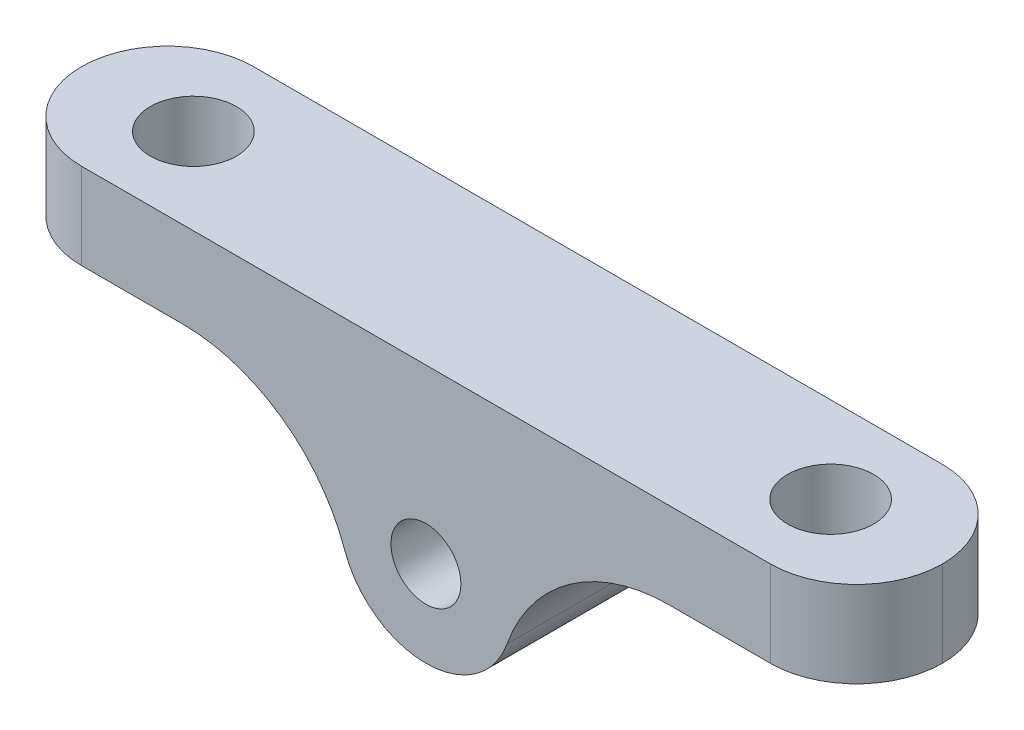
SolidWorks part; units mm, degrees
ref_plane "Front Plane" through (0, 0, 0) normal (0, 0, 1) x (1, 0, 0)
ref_plane "Top Plane" through (0, 0, 0) normal (0, 1, 0) x (1, 0, 0)
ref_plane "Right Plane" through (0, 0, 0) normal (1, 0, 0) x (0, 0, -1)
sketch "Sketch1" plane through (0, 0, 0) normal (0, 0, 1) x (1, 0, 0)
  line L0 (0, 0) -> (63.5, 0)
  line L1 (63.5, 0) -> (63.5, -6.35)
  line L2 (63.5, -6.35) -> (0, -6.35)
  line L3 (0, 0) -> (0, -6.35)
  dimension "D1" = 6.35
  dimension "D2" = 6.35
  dimension "D3" = 63.5
extrude "Boss-Extrude1" add sketch "Sketch1" along normal blind 12.7 contours L2 L3 L0 L1
sketch "Sketch2" plane through (0, 0, 0) normal (0, 1, 0) x (1, 0, 0)
  line L0 (0, 0) -> (63.5, 0) construction
  line L1 (0, -12.7) -> (0, 0) construction
  line L2 (63.5, -12.7) -> (63.5, 0) construction
  circle A0 centre (8.255, -6.35) radius 3.175
  circle A1 centre (55.245, -6.35) radius 3.175
  dimension "D1" = 6.35
  dimension "D2" = 6.35
  dimension "D3" = 6.35
  dimension "D4" = 6.35
  dimension "D5" = 8.255
  dimension "D6" = 8.255
  dimension "D7" = 46.99
extrude "Cut-Extrude1" cut sketch "Sketch2" against normal blind 26.162
fillet "Fillet1" radius 6.35 4 edges at (63.5, -3.175, 12.7) (63.5, -3.175, 0) (0, -3.175, 0) (0, -3.175, 12.7)
sketch "Sketch3" plane through (0, 0, 12.7) normal (0, 0, 1) x (1, 0, 0)
  line L0 (25.4, -6.35) -> (38.1, -6.35)
  line L1 (25.4, -12.7) -> (25.4, -6.35)
  line L2 (57.15, -6.35) -> (6.35, -6.35) construction
  line L3 (38.1, -12.7) -> (38.1, -6.35)
  line L4 (31.75, -10.1203) -> (31.75, -21.5592)
  line L5 (0, -6.35) -> (0, 0) construction
  circle A0 centre (31.75, -12.7) radius 2.5797
  arc A1 (25.4, -12.7) -> (38.1, -12.7) centre (31.75, -12.7) ccw
  line M2 (6.35, -6.35) -> (57.15, -6.35)
  dimension "D1" = 5.1594
  dimension "D2" = 6.35
  dimension "D3" = 25.4
  dimension "D4" = 6.35
extrude "Boss-Extrude2" add sketch "Sketch3" against normal blind 12.7 contours L1 A1 L3 A0 M2 region at (31.75, -6.5296, 12.7)
fillet "Fillet2" radius 12.7 2 edges at (38.1, -6.35, 6.35) (25.4, -6.35, 6.35)
